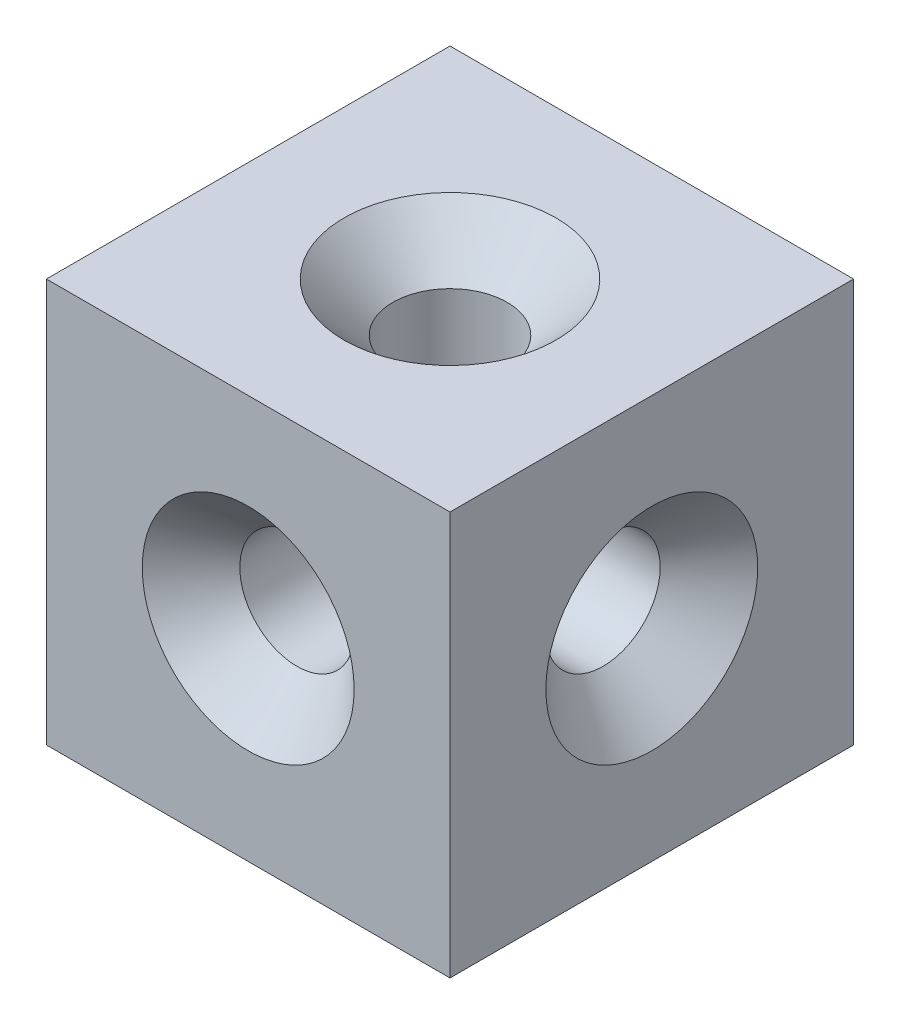
SolidWorks part; units mm, degrees
ref_plane "Front Plane" through (0, 0, 0) normal (0, 0, 1) x (1, 0, 0)
ref_plane "Top Plane" through (0, 0, 0) normal (0, 1, 0) x (1, 0, 0)
ref_plane "Right Plane" through (0, 0, 0) normal (1, 0, 0) x (0, 0, -1)
sketch "Sketch1" plane through (0, 0, 0) normal (0, 0, 1) x (1, 0, 0)
  line L1 (6, -6) -> (-6, -6)
  line L2 (6, -6) -> (6, 6)
  line L3 (6, 6) -> (-6, 6)
  line L4 (-6, -6) -> (-6, 6)
  line L5 (6, -6) -> (-6, 6) construction
  line L6 (6, 6) -> (-6, -6) construction
  point P0 (0, 0)
  dimension "D1" = 12
  dimension "D2" = 12
extrude "Boss-Extrude1" add sketch "Sketch1" along normal mid plane 12
hole_wizard "CSK for M3 Flat Head Machine Screw1" positions "Sketch3" profile "Sketch2" countersink size "M3" standard "ANSI Metric"
sketch "Sketch3" plane through (0, 0, 6) normal (0, 0, 1) x (1, 0, 0)
  point P0 (0, 0)
sketch "Sketch2" plane through (0, 0, 6) normal (1, 0, 0) x (0, -1, 0)
  line L0 (0, 0) -> (0, 7.0215)
  line L1 (0, 7.0215) -> (1.7, 6)
  line L2 (1.7, 6) -> (1.7, 1.45)
  line L3 (1.7, 1.45) -> (3.15, 0)
  line L5 (3.15, 0) -> (0, 0)
  line L6 (-1.7, 1.45) -> (-3.15, 0) construction
  line L10 (0, 7.0215) -> (-1.7, 6) construction
  line L11 (0, -6.35) -> (0, 107.95) construction
  dimension "Hole Dia." = 3.4
  dimension "Hole Depth" = 6
  dimension "Near C'Sink Dia." = 6.3
  dimension "Near C'Sink Angle" = 90
  dimension "Drill Angle" = 118
hole_wizard "CSK for M3 Flat Head Machine Screw2" positions "Sketch6" profile "Sketch7" countersink size "M3" standard "ANSI Metric"
sketch "Sketch6" plane through (6, 0, 0) normal (1, 0, 0) x (0, 0, -1)
  point P0 (0, 0)
sketch "Sketch7" plane through (6, 0, 0) normal (0, 1, 0) x (0, 0, -1)
  line L0 (0, 0) -> (0, 7.0215)
  line L1 (0, 7.0215) -> (1.7, 6)
  line L2 (1.7, 6) -> (1.7, 1.45)
  line L3 (1.7, 1.45) -> (3.15, 0)
  line L5 (3.15, 0) -> (0, 0)
  line L6 (-1.7, 1.45) -> (-3.15, 0) construction
  line L10 (0, 7.0215) -> (-1.7, 6) construction
  line L11 (0, -6.35) -> (0, 107.95) construction
  dimension "Hole Dia." = 3.4
  dimension "Hole Depth" = 6
  dimension "Near C'Sink Dia." = 6.3
  dimension "Near C'Sink Angle" = 90
  dimension "Drill Angle" = 118
hole_wizard "CSK for M3 Flat Head Machine Screw3" positions "Sketch8" profile "Sketch9" countersink size "M3" standard "ANSI Metric"
sketch "Sketch8" plane through (0, 0, -6) normal (0, 0, -1) x (-1, 0, 0)
  point P0 (0, 0)
sketch "Sketch9" plane through (0, 0, -6) normal (1, 0, 0) x (0, 1, 0)
  line L0 (0, 0) -> (0, 7.0215)
  line L1 (0, 7.0215) -> (1.7, 6)
  line L2 (1.7, 6) -> (1.7, 1.45)
  line L3 (1.7, 1.45) -> (3.15, 0)
  line L5 (3.15, 0) -> (0, 0)
  line L6 (-1.7, 1.45) -> (-3.15, 0) construction
  line L10 (0, 7.0215) -> (-1.7, 6) construction
  line L11 (0, -6.35) -> (0, 107.95) construction
  dimension "Hole Dia." = 3.4
  dimension "Hole Depth" = 6
  dimension "Near C'Sink Dia." = 6.3
  dimension "Near C'Sink Angle" = 90
  dimension "Drill Angle" = 118
hole_wizard "CSK for M3 Flat Head Machine Screw7" positions "Sketch10" profile "Sketch11" countersink size "M3" standard "ANSI Metric"
sketch "Sketch10" plane through (-6, 0, 0) normal (-1, 0, 0) x (0, 0, 1)
  point P0 (0, 0)
  point P4 (0, 0)
sketch "Sketch11" plane through (-6, 0, 0) normal (0, 1, 0) x (0, 0, 1)
  line L0 (0, 0) -> (0, 7.0215)
  line L1 (0, 7.0215) -> (1.7, 6)
  line L2 (1.7, 6) -> (1.7, 1.45)
  line L3 (1.7, 1.45) -> (3.15, 0)
  line L5 (3.15, 0) -> (0, 0)
  line L6 (-1.7, 1.45) -> (-3.15, 0) construction
  line L10 (0, 7.0215) -> (-1.7, 6) construction
  line L11 (0, -6.35) -> (0, 107.95) construction
  dimension "Hole Dia." = 3.4
  dimension "Hole Depth" = 6
  dimension "Near C'Sink Dia." = 6.3
  dimension "Near C'Sink Angle" = 90
  dimension "Drill Angle" = 118
hole_wizard "CSK for M3 Flat Head Machine Screw8" positions "Sketch12" profile "Sketch13" countersink size "M3" standard "ANSI Metric"
sketch "Sketch12" plane through (0, 6, 0) normal (0, 1, 0) x (1, 0, 0)
  point P0 (0, 0)
sketch "Sketch13" plane through (0, 6, 0) normal (1, 0, 0) x (0, 0, 1)
  line L0 (0, 0) -> (0, 7.0215)
  line L1 (0, 7.0215) -> (1.7, 6)
  line L2 (1.7, 6) -> (1.7, 1.45)
  line L3 (1.7, 1.45) -> (3.15, 0)
  line L5 (3.15, 0) -> (0, 0)
  line L6 (-1.7, 1.45) -> (-3.15, 0) construction
  line L10 (0, 7.0215) -> (-1.7, 6) construction
  line L11 (0, -6.35) -> (0, 107.95) construction
  dimension "Hole Dia." = 3.4
  dimension "Hole Depth" = 6
  dimension "Near C'Sink Dia." = 6.3
  dimension "Near C'Sink Angle" = 90
  dimension "Drill Angle" = 118
hole_wizard "CSK for M3 Flat Head Machine Screw9" positions "Sketch14" profile "Sketch15" countersink size "M3" standard "ANSI Metric"
sketch "Sketch14" plane through (0, -6, 0) normal (0, -1, 0) x (-1, 0, 0)
  point P0 (0, 0)
sketch "Sketch15" plane through (0, -6, 0) normal (1, 0, 0) x (0, 0, -1)
  line L0 (0, 0) -> (0, 7.0215)
  line L1 (0, 7.0215) -> (1.7, 6)
  line L2 (1.7, 6) -> (1.7, 1.45)
  line L3 (1.7, 1.45) -> (3.15, 0)
  line L5 (3.15, 0) -> (0, 0)
  line L6 (-1.7, 1.45) -> (-3.15, 0) construction
  line L10 (0, 7.0215) -> (-1.7, 6) construction
  line L11 (0, -6.35) -> (0, 107.95) construction
  dimension "Hole Dia." = 3.4
  dimension "Hole Depth" = 6
  dimension "Near C'Sink Dia." = 6.3
  dimension "Near C'Sink Angle" = 90
  dimension "Drill Angle" = 118
equation "\"Length\"= 283mm"
equation "\"Width\"= 225mm"
equation "\"WallThickness\"= 12.5mm"
equation "\"UpperWaterJacketThickness\"= 28mm"
equation "\"SpacerHeight\"= 80.2mm"
equation "\"SpacerCornerWidth\"= 10mm"
equation "\"SpacerCornerHeight\"= 60.16mm"
equation "\"SpacerPegDiameter\"= 10mm"
equation "\"SpacerPegHeight\"= 10mm"
equation "\"TubingShort\"= 110mm"
equation "\"TubingLong\"= 175mm"
equation "\"PlateLength\"= 252mm"
equation "\"PlateWidth\"= 190mm"
equation "\"PlateHoleDiameter\"= 5.9mm"
equation "\"PlateHoleBottom\"= 2mm"
equation "\"PlateHoleSide\"= 1.55mm"
equation "\"PlateHoleSpacing\"= 3.1mm"
equation "\"PlateThickness\"= 1.55mm"
equation "\"ReservoirBottom\"= 12.5mm"
equation "\"ReservoirSupportWidth\"= 12mm"
equation "\"ReservoirSupportHeight\"= 15.1mm"
equation "\"ReservoirSupportPlacementHeight\"= 50mm"
equation "\"ReservoirHoleDiameter\"= 12.7mm"
equation "\"ReservoirHoleRight\"= 25mm"
equation "\"ReservoirHoleTop\"= \"ReservoirSupportPlacementHeight\""
equation "\"ReservoirHeight\"= 90mm"
equation "\"ReservoirPortBottom\"= 4mm"
equation "\"ReservoirPortTop\"= 10mm"
equation "\"ReservoirPortWidth\"= 101mm"
equation "\"CustomSpacerWallThickness\"= 0.25in"
equation "\"CustomSpacerHeight\"= 5in"
equation "\"CustomSpacerRodHoleHeight\"= .75in"
equation "\"CustomSpacerRodHoleDiameter\"= .3125in"
equation "\"ScrewBlockSide\"= 12mm"
equation "\"ScrewBlockUpperHeight\"= 16mm"
equation "\"ScrewBlockLowerHeight\"= 16mm"
equation "\"InternalLength\"= \"Length\" - ( 2 * \"WallThickness\" )"
equation "\"InternalWidth\"= \"Width\" - ( 2 * \"WallThickness\" )"
equation "\"CustomSpacerPegHeight\"= 1in"
equation "\"CustomSpacerScrewBore\"=3.2mm"
equation "\"CustomSpacerScrewDepth\"=10mm"
equation "\"D1@Sketch1\"=\"ScrewBlockSide\""
equation "\"D2@Sketch1\"=\"ScrewBlockSide\""
equation "\"D1@Boss-Extrude1\"=\"ScrewBlockSide\""
